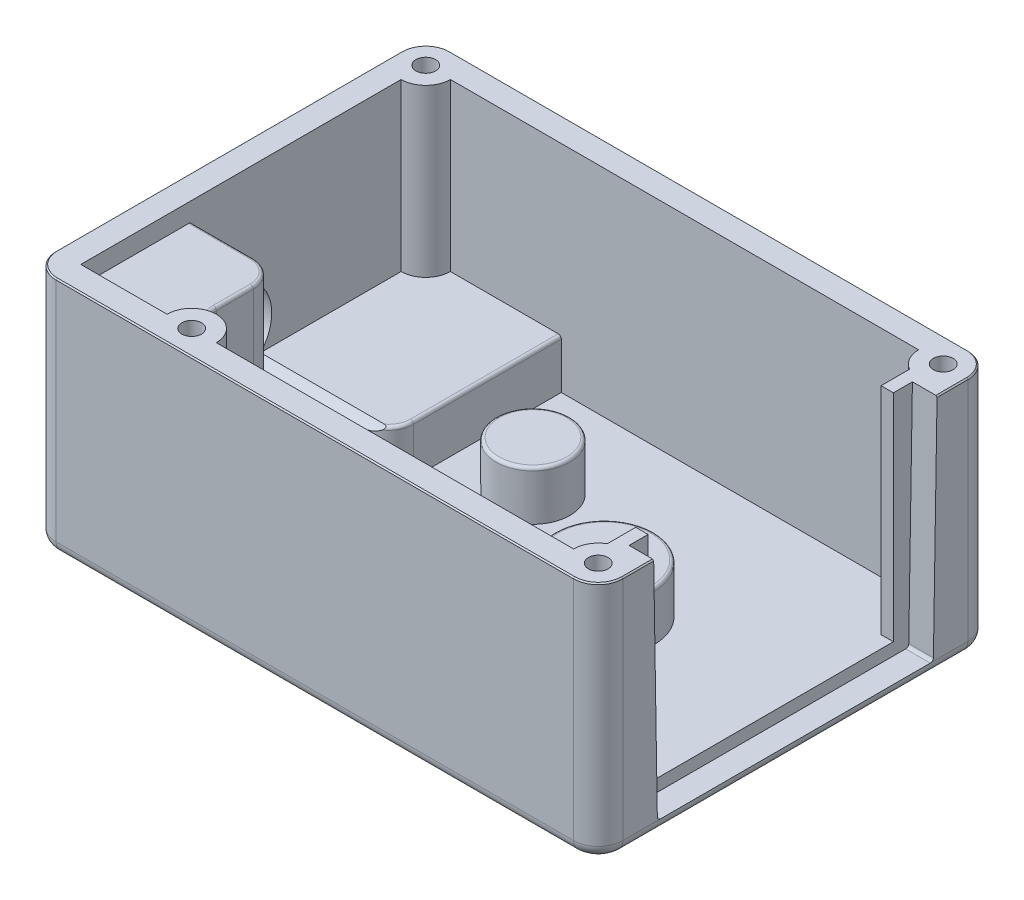
SolidWorks part; units mm, degrees
ref_plane "Front Plane" through (0, 0, 0) normal (0, 0, 1) x (1, 0, 0)
ref_plane "Top Plane" through (0, 0, 0) normal (0, 1, 0) x (1, 0, 0)
ref_plane "Right Plane" through (0, 0, 0) normal (1, 0, 0) x (0, 0, -1)
sketch "Sketch1" plane through (0, 0, 0) normal (0, 1, 0) x (1, 0, 0)
  line L0 (-38, 0) -> (22, 0) construction
  line L1 (-28.5, 16) -> (13.5, 16)
  line L2 (-30.5, 14) -> (-30.5, -14)
  line L3 (-28.5, -16) -> (13.5, -16)
  line L4 (15.5, 14) -> (15.5, -14)
  arc A0 (13.5, 16) -> (15.5, 14) centre (13.5, 14) cw
  arc A1 (13.5, -16) -> (15.5, -14) centre (13.5, -14) ccw
  arc A2 (-30.5, -14) -> (-28.5, -16) centre (-28.5, -14) ccw
  arc A3 (-28.5, 16) -> (-30.5, 14) centre (-28.5, 14) ccw
  point P13 (15.5, 0)
  dimension "D3" = 2
  dimension "D6" = 15.5
  dimension "D1" = 46
  dimension "D2" = 32
  dimension "D4" = 60
  dimension "D5" = 38
extrude "Boss-Extrude1" add sketch "Sketch1" along normal blind 19.5
fillet "Fillet1" radius 1 8 edges at (-7.5, 0, -16) (-29.9142, 0, -15.4142) (-30.5, 0, 0) (-29.9142, 0, 15.4142) (-7.5, 0, 16) (14.9142, 0, 15.4142) (15.5, 0, 0) (14.9142, 0, -15.4142)
sketch "Sketch2" plane through (0, 19.5, 0) normal (0, 1, 0) x (1, 0, 0)
  point P0 (-37.7641, 8.4607)
  point P3 (-37.7641, -9.5393)
  point P6 (-4.7641, -9.5393)
  point P9 (-4.7641, 8.4607)
sketch "Sketch3" plane through (0, 19.5, 0) normal (0, 1, 0) x (1, 0, 0)
  point P7 (13.5, -14)
  point P10 (-19.5, -14)
  point P12 (-28.5, 14)
  point P13 (13.5, 14)
  dimension "D1" = 33
  dimension "D2" = 42
  dimension "D3" = 14
  dimension "D4" = 14
  dimension "D5" = 13.5
sketch "Sketch5" plane through (0, 19.5, 0) normal (0, 1, 0) x (1, 0, 0)
  line L0 (-28.5, 12) -> (-28.5, -14)
  line L1 (-28.5, -14) -> (-21.5, -14)
  line L2 (13.5, -12) -> (13.5, 12)
  line L3 (11.5, 14) -> (-26.5, 14)
  line L12 (-17.5, -14) -> (11.5, -14)
  arc A12 (-28.5, 12) -> (-26.5, 14) centre (-28.5, 14) ccw
  arc A13 (11.5, 14) -> (13.5, 12) centre (13.5, 14) ccw
  arc A14 (13.5, -12) -> (11.5, -14) centre (13.5, -14) ccw
  arc A15 (-17.5, -14) -> (-21.5, -14) centre (-19.5, -14) ccw
  point P0 (-28.5, 14)
  point P15 (13.5, -14)
  point P18 (13.5, -14)
  point P21 (13.5, 14)
  point P22 (-28.5, 14)
  point P29 (-19.5, -14)
extrude "Cut-Extrude1" cut sketch "Sketch5" against normal blind 17.5
sketch "Sketch6" plane through (0, 0, 0) normal (0, -1, 0) x (1, 0, 0)
  line L0 (-30.5, -14) -> (-30.5, 14) construction
  line L1 (-28.5, -12) -> (-19.5, -12)
  line L2 (-30.5, -10) -> (-30.5, -2)
  line L3 (-28.5, 0) -> (-19.5, 0)
  line L4 (-17.5, -10) -> (-17.5, -2)
  line L5 (13.5, -16) -> (-28.5, -16) construction
  circle A0 centre (0, 0) radius 4
  circle A1 centre (-11.5, 5.7) radius 3
  circle A2 centre (-11.5, -5.7) radius 3
  arc A3 (-30.5, -2) -> (-28.5, 0) centre (-28.5, -2) cw
  arc A4 (-28.5, -12) -> (-30.5, -10) centre (-28.5, -10) cw
  arc A5 (-19.5, -12) -> (-17.5, -10) centre (-19.5, -10) ccw
  arc A6 (-19.5, 0) -> (-17.5, -2) centre (-19.5, -2) cw
  point P19 (-30.5, 0)
  point P22 (-30.5, -12)
  point P27 (-17.5, 0)
  dimension "D7" = 6
  dimension "D8" = 6
  dimension "D9" = 8
  dimension "D10" = 2
  dimension "D1" = 12
  dimension "D2" = 13
  dimension "D3" = 11.4
  dimension "D4" = 5.7
  dimension "D5" = 19
  dimension "D6" = 4
extrude "Boss-Extrude2" add sketch "Sketch6" along normal blind 2 and the other way blind 6
fillet "Fillet2" radius 0.25 23 edges at (-30.24, 0.3274, -10.9861) (-29.0176, 0, -11.9319) (-30.24, 0.3274, -1.0139) (-29.0176, 0, -0.0681) (-24, 0, 0) (-18.0858, 0, -0.5858) (-17.5, 0, -6) (-18.0858, 0, -11.4142) (0, -2, -4) (-11.5, -2, 2.7) (-11.5, -2, -8.7) (-24, -2, 0) (-18.0858, -2, -0.5858) (-17.5, -2, -6) (-18.0858, -2, -11.4142) (-24, -2, -12) (-29.9142, -2, -11.4142) (-30.5, -2, -6) (-29.9142, -2, -0.5858) (-24, 0, -12) (0, 0, -4) (-11.5, 0, -8.7) (-11.5, 0, 2.7)
hole_wizard "M2x0.4 Tapped Hole1" positions "Sketch7" profile "Sketch8" tap size "M2x0.4" standard "ANSI Metric"
sketch "Sketch7" plane through (0, 19.5, 0) normal (0, 1, 0) x (1, 0, 0)
  point P0 (-28.5, 14)
  point P3 (-19.5, -14)
  point P6 (13.5, -14)
  point P9 (13.5, 14)
cosmetic thread "Hole Thread1" parameters "D1"=19.5, "D2"=2
cosmetic thread "Hole Thread2" parameters "D1"=19.5, "D2"=2
cosmetic thread "Hole Thread3" parameters "D1"=19.5, "D2"=2
cosmetic thread "Hole Thread4" parameters "D1"=19.5, "D2"=2
sketch "Sketch8" plane through (-28.5, 19.5, -14) normal (1, 0, 0) x (0, 0, 1)
  line L0 (0, 0) -> (0, 8.4807)
  line L1 (0, 8.4807) -> (0.8, 8)
  line L2 (0.8, 8) -> (0.8, 0)
  line L5 (0.8, 0) -> (0, 0)
  line L10 (0, 8.4807) -> (-0.8, 8) construction
  line L11 (0, -6.35) -> (0, 107.95) construction
  dimension "Tap Drill Dia." = 1.6
  dimension "Tap Drill Depth" = 8
  dimension "Drill Angle" = 118
sketch "Sketch9" plane through (15.5, 0, 0) normal (1, 0, 0) x (0, 0, -1)
  line L0 (-11.5, 19.5) -> (11.5, 19.5)
  line L1 (-14, 19.5) -> (14, 19.5) construction
  line L2 (11.5, 19.5) -> (11.2, 1)
  line L3 (11.2, 1) -> (-11.2, 1)
  line L4 (-11.2, 1) -> (-11.5, 19.5)
  line L5 (0, -6) -> (0, 24) construction
  dimension "D1" = 30
  dimension "D2" = 6
  dimension "D3" = 23
  dimension "D4" = 11.5
  dimension "D5" = 22.4
  dimension "D6" = 11.2
  dimension "D7" = 1
  dimension "D8" = 18.5
extrude "Cut-Extrude2" cut sketch "Sketch9" against normal up to surface (2 mm away) up to face at (13.5, 10.75, 0)
fillet "Fillet3" radius 0.25 2 edges at (14.5, 1, 11.2) (14.5, 1, -11.2)
sketch "Sketch10" plane through (0, 19.5, 0) normal (0, 1, 0) x (1, 0, 0)
  line L0 (-36, 0) -> (24, 0) construction
  line L1 (13.5, 10.954) -> (13.5, -10.954) construction
  line L2 (13.5, 9.954) -> (12.5, 9.954)
  line L3 (13.5, 9.954) -> (13.5, 12)
  line L5 (12.5, 9.954) -> (12.5, 12.2679)
  line L6 (15.5, 10.954) -> (13.5, 10.954) construction
  line L12 (12.5, -9.954) -> (12.5, -12.2679)
  line L13 (13.5, -9.954) -> (13.5, -12)
  line L14 (13.5, -9.954) -> (12.5, -9.954)
  arc A0 (11.5, 14) -> (13.5, 12) centre (13.5, 14) ccw construction
  arc A1 (12.5, 12.2679) -> (13.5, 12) centre (13.5, 14) ccw
  arc A3 (12.5, -12.2679) -> (13.5, -12) centre (13.5, -14) cw
  dimension "D1" = 60
  dimension "D2" = 24
  dimension "D3" = 1
  dimension "D4" = 1
extrude "Boss-Extrude3" add sketch "Sketch10" against normal up to surface (17.5 mm away) up to face at (-9.2241, 2, -0.5991)
sketch "Sketch11" plane through (-30.5, 0, 0) normal (-1, 0, 0) x (0, 0, 1)
  line L0 (-19.9844, 8.35) -> (20.0156, 8.35) construction
  line L1 (-12.0156, 0) -> (-14, 0) construction
  line L2 (2, 21.5452) -> (2, -4.373) construction
  line L3 (16, 19.5) -> (16, 1) construction
  line L4 (-12.1421, -5.7921) -> (16.1421, 22.4921) construction
  circle A0 centre (2, 8.35) radius 12.2 construction
  circle A1 centre (2, 8.35) radius 8.5 construction
  point P14 (8.0104, 14.3604)
  point P15 (-4.0104, 2.3396)
  point P16 (2, 8.35)
  dimension "D5" = 24.4
  dimension "D8" = 17
  dimension "D1" = 40
  dimension "D2" = 20
  dimension "D3" = 8.35
  dimension "D4" = 14
  dimension "D6" = 40
  dimension "D7" = 45
hole_wizard "M3x0.5 Tapped Hole1" positions "Sketch13" profile "Sketch14" tap size "M3x0.5" standard "ANSI Metric"
sketch "Sketch13" plane through (-30.5, 0, 0) normal (-1, 0, 0) x (0, 0, 1)
  point P0 (-4.0104, 2.3396)
  point P3 (8.0104, 14.3604)
sketch "Sketch14" plane through (-30.5, 2.3396, -4.0104) normal (0, 1, 0) x (0, 0, 1)
  line L0 (0, 0) -> (0, 8.2511)
  line L1 (0, 8.2511) -> (1.25, 7.5)
  line L2 (1.25, 7.5) -> (1.25, 0)
  line L5 (1.25, 0) -> (0, 0)
  line L10 (0, 8.2511) -> (-1.25, 7.5) construction
  line L11 (0, -6.35) -> (0, 107.95) construction
  dimension "Tap Drill Dia." = 2.5
  dimension "Tap Drill Depth" = 7.5
  dimension "Drill Angle" = 118
cosmetic thread "Hole Thread5" parameters "D1"=6, "D2"=3
cosmetic thread "Hole Thread6" parameters "D1"=6, "D2"=3
hole_wizard "Ø7.0 (7) Diameter Hole1" positions "Sketch15" profile "Sketch17" hole size "Ø7.0" standard "ANSI Metric"
sketch "Sketch15" plane through (-30.5, 0, 0) normal (-1, 0, 0) x (0, 0, 1)
  point P0 (2, 8.35)
sketch "Sketch17" plane through (-30.5, 8.35, 2) normal (0, 1, 0) x (0, 0, 1)
  line L0 (0, 0) -> (0, 15.102)
  line L1 (0, 15.102) -> (3.5, 12.999)
  line L2 (3.5, 12.999) -> (3.5, 0)
  line L5 (3.5, 0) -> (0, 0)
  line L10 (0, 15.102) -> (-3.5, 12.999) construction
  line L11 (0, -6.35) -> (0, 107.95) construction
  dimension "Hole Dia." = 7
  dimension "Hole Depth" = 12.999
  dimension "Drill Angle" = 118
sketch "Sketch18" plane through (0, 2, 0) normal (0, 1, 0) x (1, 0, 0)
  line L0 (15.5, -10.954) -> (15.5, 10.954) construction
  line L1 (-28.5, -5) -> (-23.5, -5)
  line L2 (-28.5, -5) -> (-28.5, -14)
  line L4 (-21.5, -7) -> (-21.5, -10)
  line L5 (13.5, 9.954) -> (12.5, 9.954) construction
  line L6 (-28.5, -14) -> (-21.5, -14) construction
  line L7 (-28.5, -14) -> (-21.5, -14)
  arc A1 (-23.5, -5) -> (-21.5, -7) centre (-23.5, -7) cw
  arc A2 (-17.5, -14) -> (-21.5, -14) centre (-19.5, -14) ccw construction
  arc A3 (-17.5, -14) -> (-21.5, -14) centre (-19.5, -14) ccw construction
  arc A4 (-19.5, -12) -> (-21.5, -14) centre (-19.5, -14) ccw
  arc A5 (-21.5, -10) -> (-19.5, -12) centre (-19.5, -10) ccw
  point P23 (-21.5, -10.6834)
  point P28 (-21.5, -5)
  dimension "D4" = 14.954
  dimension "D1" = 2
  dimension "D3" = 4
  dimension "D2" = 35
  dimension "D5" = 20.6375
extrude "Boss-Extrude4" add sketch "Sketch18" along normal blind 16
sketch "Sketch19" plane through (0, 2, 0) normal (0, 1, 0) x (1, 0, 0)
  line L0 (11.5, 14) -> (-26.5, 14) construction
  line L1 (-19.5, 12) -> (-28.5, 12) construction
  line L2 (-17.5, 14) -> (-26.5, 14)
  line L3 (-19.5, 12) -> (-28.5, 12)
  line L4 (-17.5, 10) -> (-17.5, 14)
  arc A0 (-28.5, 12) -> (-26.5, 14) centre (-28.5, 14) ccw construction
  arc A1 (-28.5, 12) -> (-26.5, 14) centre (-28.5, 14) ccw
  arc A2 (-17.5, 10) -> (-19.5, 12) centre (-19.5, 10) ccw construction
  arc A3 (-17.5, 10) -> (-19.5, 12) centre (-19.5, 10) ccw
extrude "Boss-Extrude5" add sketch "Sketch19" along normal up to surface (4 mm away) up to face at (-21.5041, 6, -6.2574)
fillet "Fillet4" radius 0.25 9 edges at (-17.6501, 6, -1.2398) (-20.9142, 18, 11.4142) (-26, 18, 5) (-22.0858, 18, 5.5858) (0, 6, -4) (-11.5, 6, -8.7) (-11.5, 6, 2.7) (-17.5, 6, -8) (-21.5, 18, 8.5)
chamfer "Chamfer1" distance 0.1 angle 45 9 edges at (15.5, 19.5, 12.75) (14.9142, 19.5, 15.4142) (15.5, 19.5, -12.75) (14.9142, 19.5, -15.4142) (-7.5, 19.5, -16) (-29.9142, 19.5, -15.4142) (-30.5, 19.5, 0) (-29.9142, 19.5, 15.4142) (-7.5, 19.5, 16)
scale "Scale1" scale about centroid uniform scaling yes scale factor 1.5
equation "\"D4@Sketch6\"=\"D3@Sketch6\"/2"
equation "\"D8@Sketch6\"=\"D7@Sketch6\""
equation "\"D4@Sketch9\"=\"D3@Sketch9\"/2"
equation "\"D6@Sketch9\"=\"D5@Sketch9\"/2"
equation "\"D2@Sketch11\"=\"D1@Sketch11\"/2"
